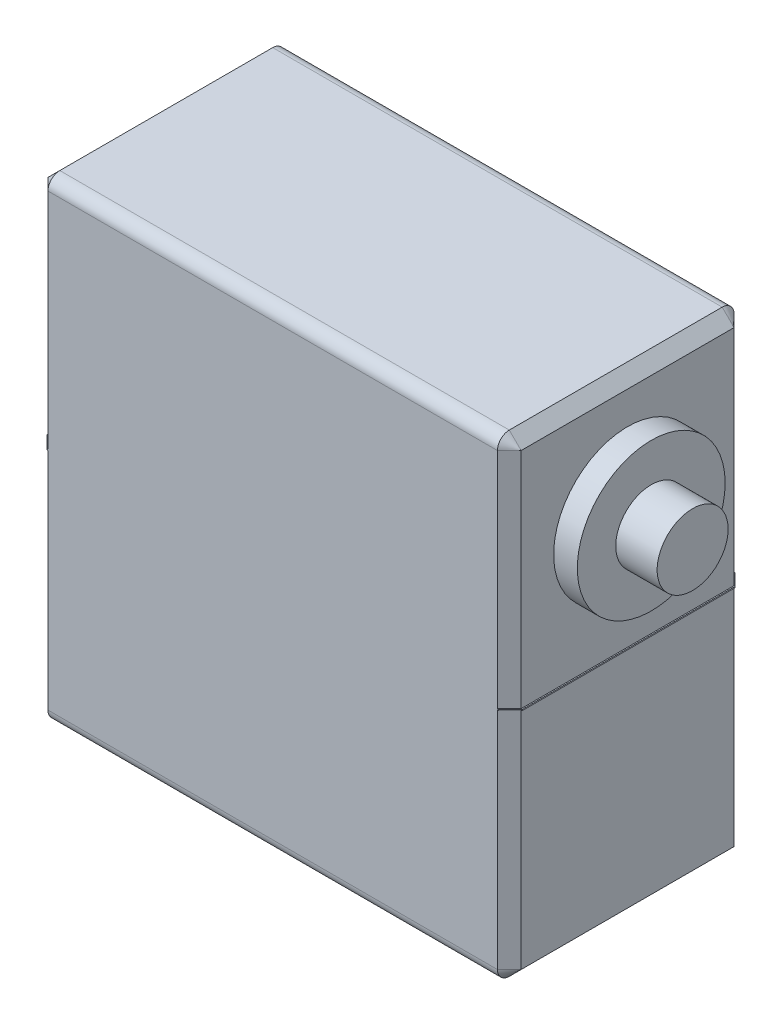
SolidWorks part; units mm, degrees
ref_plane "Спереди" through (0, 0, 0) normal (0, 0, 1) x (1, 0, 0)
ref_plane "Сверху" through (0, 0, 0) normal (0, 1, 0) x (1, 0, 0)
ref_plane "Справа" through (0, 0, 0) normal (1, 0, 0) x (0, 0, -1)
sketch "Sketch1" plane through (0, 0, 0) normal (0, 0, 1) x (1, 0, 0)
  line L0 (0, 0) -> (-20, 20) construction
  line L1 (20, 0) -> (20, 20)
  line L2 (20, 20) -> (-20, 20)
  line L3 (-20, 20) -> (-20, -20)
  line L4 (-20, -20) -> (20, -20)
  line L5 (20, -20) -> (20, 0)
  line L6 (0, 0) -> (20, -20) construction
  line L7 (0, 0) -> (20, 20) construction
  line L8 (0, 0) -> (-20, -20) construction
  dimension "D1" = 40
extrude "Основа" add sketch "Sketch1" along normal blind 20
sketch "Sketch2" plane through (20, 0, 0) normal (1, 0, 0) x (0, 0, -1)
  line L0 (-10, 10) -> (-10, 0) construction
  line L1 (-10, 0) -> (0, 0) construction
  line L2 (0, -20) -> (0, 20) construction
  circle A0 centre (-10, 10) radius 6.25
  dimension "D1" = 12.5
  dimension "D2" = 10
  dimension "D3" = 10
extrude "Выступы под ось" add sketch "Sketch2" along normal blind 2 and the other way blind 42
sketch "Sketch3" plane through (22, 0, 0) normal (1, 0, 0) x (0, 0, -1)
  circle A0 centre (-10, 10) radius 3
  dimension "D1" = 6
extrude "Ось" add sketch "Sketch3" along normal blind 3.5 and the other way blind 47.5
sketch "Sketch5" plane through (-20, 0, 0) normal (-1, 0, 0) x (0, 0, 1)
  line L0 (0, 0) -> (0, 0.1)
  line L1 (20, 20) -> (20, -20) construction
  line L2 (20, 0) -> (0, 0)
  line L3 (0, 20) -> (0, -20) construction
  line L4 (0, 0.1) -> (20, 0.1)
  line L5 (20, 0.1) -> (20, 0)
  dimension "D1" = 0.1
  dimension "D2" = 0.1
extrude "Рейка для выравнивания сборки" add sketch "Sketch5" along normal blind 0.1 and the other way blind 40.1
sketch "Sketch7" plane through (0, 0, 0) normal (0, 0, -1) x (-1, 0, 0)
  line L0 (0, 0) -> (-14, 0) construction
  text T0 "RDS315mg"
  dimension "D1" = 14
extrude "Модель сервы" cut sketch "Sketch7" against normal blind 0.3
fillet "Fillet1" radius 1 4 edges at (0, -20, 20) (0, -20, 0) (0, 20, 20) (0, 20, 0)
chamfer "Chamfer1" distance 1 angle 45 20 edges at (20, -19.7071, 0.2929) (20, -9.5, 0) (20, -20, 10) (20, -19.7071, 19.7071) (20, -9.5, 20) (20, 9.55, 0) (20, 19.7071, 0.2929) (20, 9.55, 20) (20, 19.7071, 19.7071) (20, 20, 10) (-20, -9.5, 20) (-20, -19.7071, 19.7071) (-20, -20, 10) (-20, -19.7071, 0.2929) (-20, -9.5, 0) (-20, 9.55, 20) (-20, 19.7071, 19.7071) (-20, 20, 10) (-20, 19.7071, 0.2929) (-20, 9.55, 0)
chamfer "Chamfer2" distance 1 angle 45 4 edges at (20.1, 0.05, 0) (20.1, 0.05, 20) (-20.1, 0.05, 20) (-20.1, 0.05, 0)
